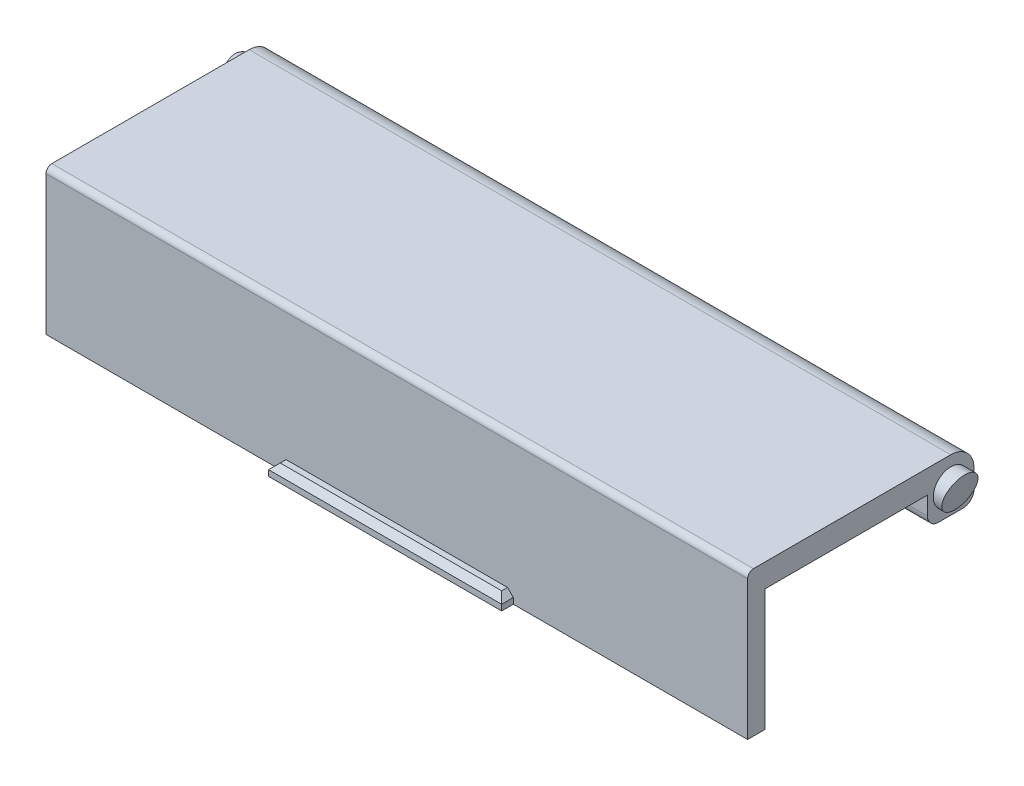
SolidWorks part; units mm, degrees
ref_plane "Front Plane" through (0, 0, 0) normal (0, 0, 1) x (1, 0, 0)
ref_plane "Top Plane" through (0, 0, 0) normal (0, 1, 0) x (1, 0, 0)
ref_plane "Right Plane" through (0, 0, 0) normal (1, 0, 0) x (0, 0, -1)
sketch "Sketch1" plane through (0, 0, 0) normal (1, 0, 0) x (0, 0, -1)
  line L0 (0, -10.446) -> (0, 0)
  line L1 (0, 0) -> (13.931, 0)
  line L2 (13.931, 0) -> (13.931, -2.5)
  line L3 (13.931, -2.5) -> (17.931, -2.5)
  line L4 (17.931, -2.5) -> (17.931, 2)
  line L5 (17.931, 2) -> (-1.5, 2)
  line L6 (-1.5, 2) -> (-1.5, -10.446)
  line L7 (-1.5, -10.446) -> (0, -10.446)
  dimension "D1" = 1.5
  dimension ".65" = 12.446
  dimension "D3" = 4
  dimension "D4" = 2.5
  dimension "D5" = 19.431
  dimension "D6" = 2
extrude "Boss-Extrude1" add sketch "Sketch1" along normal mid plane 60.198
fillet "Fillet1" radius 2 1 edges at (0, 2, -17.931)
sketch "Sketch2" plane through (0, 0, 0) normal (1, 0, 0) x (0, 0, -1)
  line L1 (-1.5, -10.446) -> (-2.5, -10.446)
  line L2 (-1.5, -10.446) -> (-1.5, -9.446)
  line L3 (-1.5, -9.446) -> (-2.5, -9.446)
  line L4 (-2.5, -10.446) -> (-2.5, -9.446)
  dimension "D1" = 1
extrude "Boss-Extrude2" add sketch "Sketch2" along normal mid plane 20
sketch "Sketch3" plane through (30.099, 0, 0) normal (1, 0, 0) x (0, 0, -1)
  line L0 (13.931, -2.5) -> (17.931, -2.5) construction
  circle A0 centre (15.931, -0.4) radius 1.5
  dimension "D1" = 3
  dimension "D2" = 2
  dimension "D3" = 2.1
extrude "Boss-Extrude3" add sketch "Sketch3" along normal blind 1.2
mirror "Mirror1" about plane through (0, 0, 0) normal (1, 0, 0) of "Boss-Extrude3"
chamfer "Chamfer1" distance 0.5 angle 45 3 edges at (-10, -9.446, 2) (10, -9.446, 2) (0, -9.446, 2.5)
fillet "Fillet3" radius 0.5 1 edges at (0, 2, 1.5)
sketch "Sketch7" plane through (0, 0, 1.5) normal (0, 0, 1) x (1, 0, 0)
  line L0 (7.695, 27.3237) -> (140.3617, 27.3237) construction
  line L1 (-30.2633, -2.8229) -> (-30.2633, -4.6928)
  line L2 (-30.2633, -4.6928) -> (-31.5821, -4.6928)
  line L3 (-31.5821, -4.6928) -> (-31.5821, -0.3107)
  line L4 (-31.5821, -0.3107) -> (-29.6366, -0.3107)
  line L5 (-30.2633, -2.2096) -> (-30.2633, -0.8264)
  line L6 (-28.2011, -3.3328) -> (-28.2011, -4.6928)
  line L7 (-28.2011, -4.6928) -> (-29.4478, -4.6928)
  line L8 (-29.4478, -4.6928) -> (-29.4478, -3.3328)
  line L9 (-26.134, -2.4358) -> (-26.134, -3.7851) construction
  line L10 (-25.6426, -2.4358) -> (-25.6426, -2.6977)
  line L11 (-26.6254, -2.4358) -> (-26.6254, -2.6977)
  line L12 (-23.5277, -1.9664) -> (-23.5277, -4.6667)
  line L13 (-24.2562, -1.4682) -> (-23.5277, -1.4682)
  line L14 (-24.2562, -1.4682) -> (-24.2562, -1.9664)
  line L15 (-24.2562, -1.9664) -> (-23.5277, -1.9664)
  line L16 (-21.5475, -1.4682) -> (-21.5475, -1.9664)
  line L17 (-23.5277, -0.8569) -> (-22.2843, -0.8569)
  line L18 (-23.5277, -0.8569) -> (-23.5277, -1.4682)
  line L19 (-23.5277, -4.6667) -> (-22.2843, -4.6667)
  line L20 (-22.2843, -0.8569) -> (-22.2843, -1.4682)
  line L21 (-22.2843, -1.4682) -> (-21.5475, -1.4682)
  line L22 (-22.2843, -1.9664) -> (-22.2843, -4.6667)
  line L23 (-22.2843, -1.9664) -> (-21.5475, -1.9664)
  line L24 (-29.5308, -0.988) -> (-29.5308, -1.9664)
  line L25 (-21.313, -1.5938) -> (-19.9566, -1.5938)
  line L26 (-21.313, -1.5938) -> (-21.313, -4.6667)
  line L27 (-21.313, -4.6667) -> (-19.9566, -4.6667)
  line L28 (-19.9566, -1.5938) -> (-19.9566, -2.0894)
  line L29 (-12.3495, -0.2259) -> (-10.6322, -0.2259)
  line L30 (-12.3495, -0.2259) -> (-12.3495, -4.6407)
  line L31 (-12.3495, -4.6407) -> (-11.1172, -4.6407)
  line L32 (-11.1172, -4.6407) -> (-11.1172, -2.9238)
  line L33 (-8.9022, -0.1203) -> (-7.4323, -0.1203)
  line L34 (-8.9022, -0.1203) -> (-8.9022, -1.1066)
  line L35 (-8.9022, -1.1066) -> (-7.4323, -1.1066)
  line L36 (-7.4323, -0.1203) -> (-7.4323, -1.1066)
  line L37 (-8.907, -1.5938) -> (-7.4323, -1.5938)
  line L38 (-8.907, -1.5938) -> (-8.907, -4.664)
  line L39 (-8.907, -4.664) -> (-7.4323, -4.664)
  line L40 (-7.4323, -1.5938) -> (-7.4323, -4.664)
  line L41 (-24.4919, -2.6294) -> (-24.4919, -3.1934)
  line L42 (-17.6786, -2.3552) -> (-17.6786, -2.5863) construction
  line L43 (-24.4919, -3.4389) -> (-25.6426, -3.4389)
  line L44 (-24.4919, -3.1934) -> (-26.6254, -3.1934)
  line L45 (-19.1018, -2.5863) -> (-18.1131, -2.5863)
  line L46 (-18.1131, -2.5863) -> (-18.1131, -2.2096)
  line L47 (-19.9566, -2.5595) -> (-19.9566, -4.6667)
  line L48 (-16.1521, -2.4557) -> (-16.1521, -3.805) construction
  line L49 (-15.6608, -2.4557) -> (-15.6608, -3.805)
  line L50 (-16.6435, -2.4557) -> (-16.6435, -3.805)
  line L51 (-26.6254, -2.6977) -> (-25.6426, -2.6977)
  line L52 (-24.4919, -3.4389) -> (-24.4919, -3.6194)
  line L53 (-25.6426, -3.4389) -> (-25.6426, -3.7851)
  line L54 (-26.6254, -3.1934) -> (-26.6254, -3.7851)
  line L55 (-10.7458, -0.988) -> (-10.7458, -2.0894) construction
  line L56 (-10.3735, -0.988) -> (-10.3735, -2.0894)
  line L57 (-11.118, -0.988) -> (-11.118, -2.0894)
  line L58 (-11.1172, -2.9238) -> (-10.3913, -2.9238)
  arc A0 (-15.6608, -2.4557) -> (-16.6435, -2.4557) centre (-16.1521, -2.4557) ccw
  arc A1 (-16.6435, -3.805) -> (-15.6608, -3.805) centre (-16.1521, -3.805) ccw
  arc A2 (-25.6426, -2.4358) -> (-26.6254, -2.4358) centre (-26.134, -2.4358) ccw
  arc A3 (-26.6254, -3.7851) -> (-25.6426, -3.7851) centre (-26.134, -3.7851) ccw
  arc A4 (-10.3735, -0.988) -> (-11.118, -0.988) centre (-10.7458, -0.988) ccw
  arc A5 (-11.118, -2.0894) -> (-10.3735, -2.0894) centre (-10.7458, -2.0894) ccw
  ellipse E0 centre (-16.1521, -3.1341) end of major axis (-17.8866, -3.0849) minor radius 1.5332
  ellipse E1 centre (-26.134, -3.1142) end of major axis (-24.3995, -3.1634) minor radius 1.5332 (-24.4919, -2.6294) -> (-24.4919, -3.6194) ccw
  spline S0 degree 3 poles (-29.6366, -0.3107) (-29.1367, -0.3107) (-28.4721, -0.6107) (-28.0426, -1.7411) (-28.4049, -2.5033) (-28.8544, -2.6977) knots 0 0 0 0 0.382534 0.585861 1 1 1 1
  spline S1 degree 3 poles (-28.8544, -2.6977) (-28.6401, -2.6707) (-28.2847, -2.8632) (-28.2011, -3.1887) (-28.2011, -3.3328) knots 0 0 0 0 0.61778 1 1 1 1
  spline S2 degree 3 poles (-30.2633, -2.8229) (-29.648, -2.8443) (-29.4478, -3.04) (-29.4478, -3.3328) knots 0 0 0 0 1 1 1 1
  spline S3 degree 3 poles (-30.2633, -0.8264) (-30.2633, -0.5805) (-29.5308, -0.5238) (-29.5308, -0.988) knots 0 0 0 0 1 1 1 1
  spline S4 degree 3 poles (-30.2633, -2.2096) (-30.2633, -2.4029) (-29.5308, -2.4124) (-29.5308, -1.9664) knots 0 0 0 0 1 1 1 1
  spline S5 degree 3 poles (-10.6322, -0.2259) (-10.0341, -0.2259) (-9.0833, -0.8806) (-9.2252, -2.5118) (-9.8323, -2.9238) (-10.3913, -2.9238) knots 0 0 0 0 0.403061 0.503061 1 1 1 1
  spline S8 degree 3 poles (-19.9566, -2.0894) (-19.5799, -1.4836) (-18.698, -1.4592) (-18.1131, -2.0554) (-18.1131, -2.2096) knots 0 0 0 0 0.802412 1 1 1 1
  spline S9 degree 3 poles (-19.9566, -2.5595) (-19.9566, -1.9923) (-19.0995, -2.1358) (-19.1018, -2.5863) knots 0 0 0 0 1 1 1 1
  point P58 (-26.134, -3.1105)
  point P84 (-16.1521, -3.1304)
  point P102 (-10.7458, -1.5387)
extrude "Cut-Extrude1" [suppressed] cut sketch "Sketch7" against normal blind 0.5 contours L40 L37 L38 L39 | L36 L33 L34 L35 | E0 A1 L50 A0 L49 | L47 S9 L45 L46 S8 L28 L25 L26 L27 | L22 L23 L16 L21 L20 L17 L18 L13 L14 L15 L12 L19 | L41 E1 L52 L43 L53 A3 L54 L44 A2 L10 L51 L11 | L1 S2 L8 L7 L6 S1 S0 L4 L3 L2 S4 L5 S3 L24 | S5 L29 L30 L31 L32 L58 A5 L57 A4 L56
fillet "Fillet4" radius 0.9525 2 edges at (0, -2.5, -13.931) (0, -2.5, -17.931)
sketch "Sketch8" plane through (0, 0, 1.5) normal (0, 0, 1) x (1, 0, 0)
  line L0 (30.4664, -1.9) -> (31.299, 1.1)
  line L1 (30.099, -1.9) -> (31.299, -1.9) construction
  line L2 (31.299, 1.1) -> (31.299, -1.9)
  line L3 (31.299, -1.9) -> (30.4664, -1.9)
  line L4 (0, 0) -> (0, -4.1801) construction
  line L5 (-31.299, -1.9) -> (-30.4664, -1.9)
  line L6 (-31.299, 1.1) -> (-31.299, -1.9)
  line L7 (-30.4664, -1.9) -> (-31.299, 1.1)
  line L9 (-31.299, -1.9) -> (-30.099, -1.9) construction
extrude "Cut-Extrude2" cut sketch "Sketch8" against normal through all both and the other way through all
